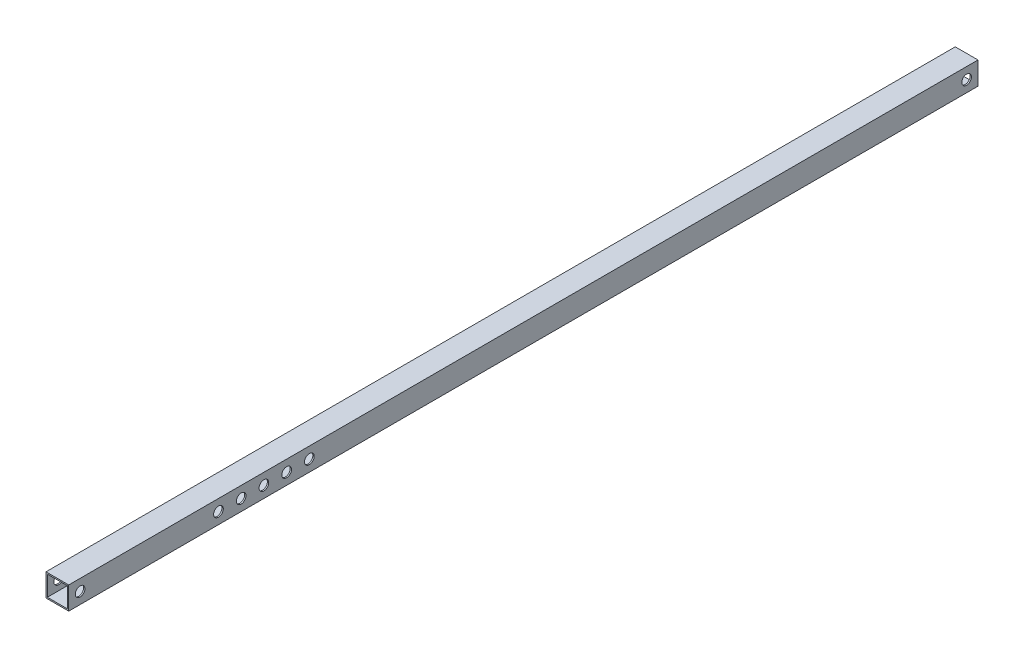
SolidWorks part; units mm, degrees
ref_plane "Front Plane" through (0, 0, 0) normal (0, 0, 1) x (1, 0, 0)
ref_plane "Top Plane" through (0, 0, 0) normal (0, 1, 0) x (1, 0, 0)
ref_plane "Right Plane" through (0, 0, 0) normal (1, 0, 0) x (0, 0, -1)
sketch "Sketch1" plane through (0, 0, 0) normal (0, 0, 1) x (1, 0, 0)
  line L0 (-8.8, -8.8) -> (-8.8, 8.8)
  line L1 (10, -10) -> (-10, -10)
  line L2 (10, -10) -> (10, 10)
  line L3 (10, 10) -> (-10, 10)
  line L4 (-10, -10) -> (-10, 10)
  line L5 (10, -10) -> (-10, 10) construction
  line L6 (10, 10) -> (-10, -10) construction
  line L7 (8.8, 8.8) -> (-8.8, 8.8)
  line L8 (8.8, -8.8) -> (8.8, 8.8)
  line L9 (8.8, -8.8) -> (-8.8, -8.8)
  point P0 (0, 0)
  dimension "D1" = 20
  dimension "D2" = 1.2
extrude "Boss-Extrude1" add sketch "Sketch1" along normal blind 800
sketch "Sketch2" plane through (10, 0, 0) normal (1, 0, 0) x (0, 0, -1)
  line L0 (0, -10) -> (0, 10) construction
  line L1 (0, 0) -> (-800, 0) construction
  line L2 (-800, -10) -> (-800, 10) construction
  circle A0 centre (-10, 0) radius 4.25
  circle A1 centre (-790, 0) radius 4.25
  dimension "D1" = 8.5
  dimension "D2" = 10
  dimension "D3" = 10
extrude "Cut-Extrude1" cut sketch "Sketch2" against normal through all
sketch "Sketch3" plane through (-10, 0, 0) normal (-1, 0, 0) x (0, 0, 1)
  line L0 (136.9908, -105.3487) -> (628.2657, 0) construction
  line L1 (-0.5, 0) -> (38.5834, 0) construction
  line L3 (0, 10) -> (0, -10) construction
  circle A0 centre (136.9908, -105.3487) radius 502.4434 construction
  circle A1 centre (628.2657, 0) radius 4.25 construction
  circle A2 centre (628.2657, 0) radius 4.25 construction
  circle A3 centre (628.2657, 0) radius 4.25
  circle A4 centre (648.2657, 0) radius 4.25
  circle A5 centre (668.2657, 0) radius 4.25
  circle A6 centre (628.2657, 0) radius 4.25
  circle A7 centre (648.2657, 0) radius 4.25
  circle A8 centre (608.2657, 0) radius 4.25
  circle A9 centre (628.2657, 0) radius 4.25
  circle A10 centre (608.2657, 0) radius 4.25
  circle A11 centre (588.2657, 0) radius 4.25
  point P11 (0, 0)
  dimension "D1" = 8.5
  dimension "D2" = 3
  dimension "D3" = 3
extrude "Cut-Extrude2" cut sketch "Sketch3" against normal through all contours A11 | A8 | A4 | A5 | A3 region at (-10, 0, 628.2657) region at (-10, 0, 648.2657) region at (-10, 0, 668.2657) region at (-10, 0, 608.2657) region at (-10, 0, 588.2657)
